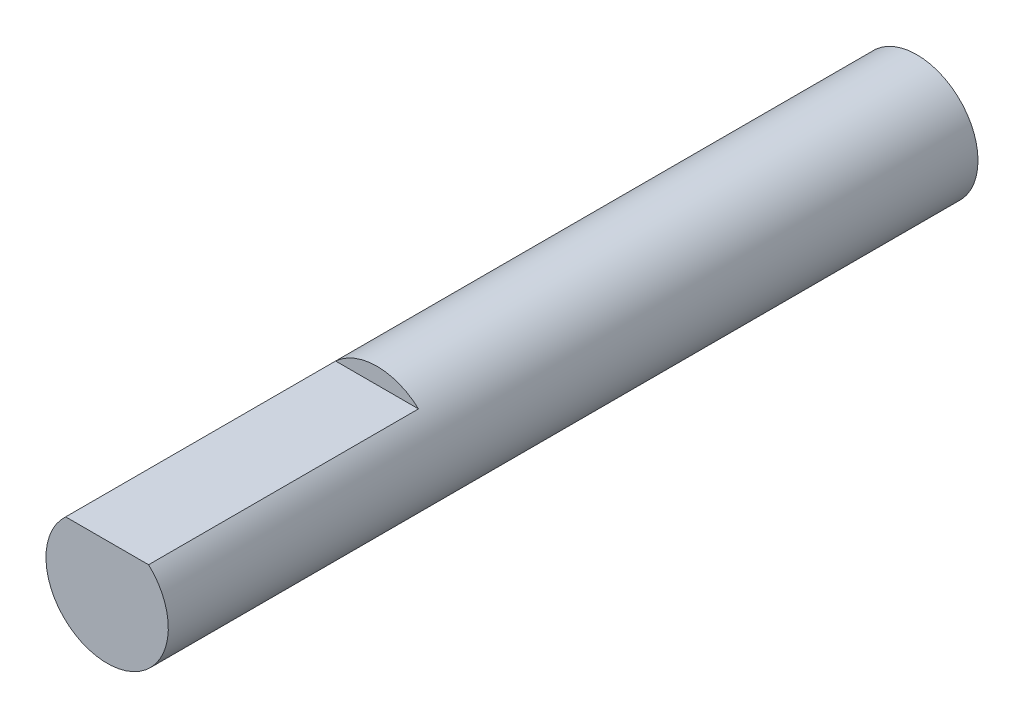
SolidWorks part; units mm, degrees
material "AISI Type 316L stainless steel"
ref_plane "Front Plane" through (0, 0, 0) normal (0, 0, 1) x (1, 0, 0)
ref_plane "Top Plane" through (0, 0, 0) normal (0, 1, 0) x (1, 0, 0)
ref_plane "Right Plane" through (0, 0, 0) normal (1, 0, 0) x (0, 0, -1)
sketch "Sketch1" plane through (0, 0, 0) normal (0, 0, 1) x (1, 0, 0)
  line L0 (11.7061, 12.7) -> (-11.7061, 12.7)
  circle A0 centre (0, 0) radius 17.272
  dimension "D1" = 34.544
  dimension "D2" = 12.7
extrude "Boss-Extrude1" add sketch "Sketch1" along normal blind 76.2 contours L0 A0 region at (0, -1.2381, 0)
extrude "Boss-Extrude2" add sketch "Sketch1<4>" against normal blind 152.4 contours L0 A0 | L0 A0 region at (0, -1.2381, 0) region at (0, 14.5513, 0)
sketch "Sketch1<4>" plane through (0, 0, 0) normal (0, 0, 1) x (1, 0, 0) same geometry as "Sketch1"
